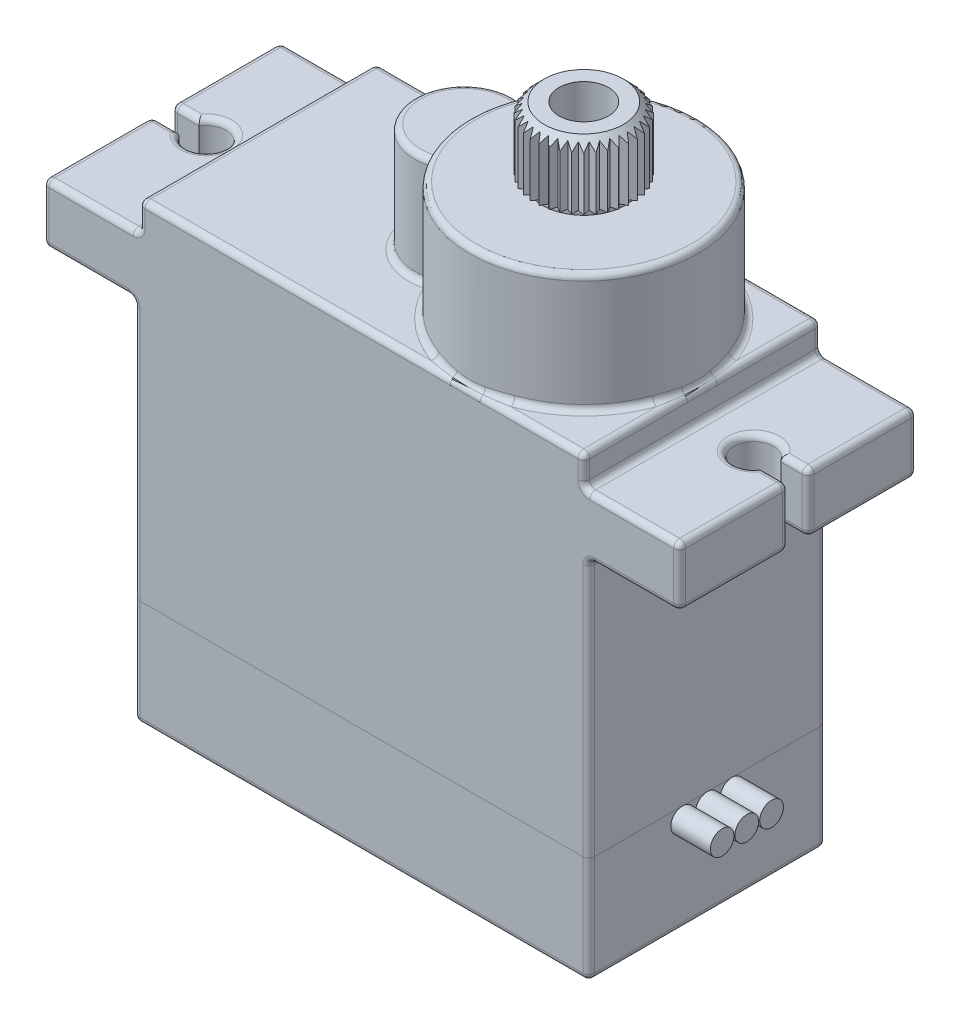
SolidWorks part; units mm, degrees
ref_plane "Front Plane" through (0, 0, 0) normal (0, 0, 1) x (1, 0, 0)
ref_plane "Top Plane" through (0, 0, 0) normal (0, 1, 0) x (1, 0, 0)
ref_plane "Right Plane" through (0, 0, 0) normal (1, 0, 0) x (0, 0, -1)
sketch "Sketch1" plane through (0, 0, 0) normal (0, 1, 0) x (1, 0, 0)
  line L1 (-11.5, -6) -> (11.5, -6)
  line L2 (-11.5, -6) -> (-11.5, 6)
  line L3 (-11.5, 6) -> (11.5, 6)
  line L4 (11.5, -6) -> (11.5, 6)
  line L5 (-11.5, -6) -> (11.5, 6) construction
  line L6 (-11.5, 6) -> (11.5, -6) construction
  point P0 (0, 0)
  dimension "D1" = 12
  dimension "D2" = 23
extrude "Boss-Extrude1" add sketch "Sketch1" along normal blind 18.5
sketch "Sketch2" plane through (0, 18.5, 0) normal (0, 1, 0) x (1, 0, 0)
  line L0 (11.5, 6) -> (-11.5, 6) construction
  line L1 (-16.1, -6) -> (16.1, -6)
  line L2 (-16.1, -6) -> (-16.1, 6)
  line L3 (-16.1, 6) -> (16.1, 6)
  line L4 (16.1, -6) -> (16.1, 6)
  line L5 (-16.1, -6) -> (16.1, 6) construction
  line L6 (-16.1, 6) -> (16.1, -6) construction
  point P0 (0, 0)
  dimension "D1" = 32.2
extrude "Boss-Extrude2" add sketch "Sketch2" along normal blind 3
sketch "Sketch3" plane through (0, 21.5, 0) normal (0, 1, 0) x (1, 0, 0)
  line L0 (16.1, 6) -> (-16.1, 6) construction
  line L1 (-11.25, -6) -> (11.25, -6)
  line L2 (-11.25, -6) -> (-11.25, 6)
  line L3 (-11.25, 6) -> (11.25, 6)
  line L4 (11.25, -6) -> (11.25, 6)
  line L5 (-11.25, -6) -> (11.25, 6) construction
  line L6 (-11.25, 6) -> (11.25, -6) construction
  point P0 (0, 0)
  dimension "D1" = 22.5
extrude "Boss-Extrude3" add sketch "Sketch3" along normal blind 1.5
sketch "Sketch4" plane through (0, 23, 0) normal (0, 1, 0) x (1, 0, 0)
  line L0 (-11.25, 6) -> (-11.25, -6) construction
  line L1 (5.25, 5.75) -> (5.25, 6) construction
  line L2 (11.25, 6) -> (-11.25, 6) construction
  line L3 (11, 0) -> (11.25, 0) construction
  line L4 (11.25, -6) -> (11.25, 6) construction
  line L5 (5.25, -5.75) -> (5.25, -6) construction
  line L6 (-11.25, -6) -> (11.25, -6) construction
  circle A0 centre (5.25, 0) radius 5.75
  point P5 (-11.25, 0)
  dimension "D1" = 11.5
extrude "Boss-Extrude4" add sketch "Sketch4" along normal blind 6
sketch "Sketch5" plane through (0, 23, 0) normal (0, 1, 0) x (1, 0, 0)
  line L0 (-11.25, 6) -> (-11.25, -6) construction
  circle A0 centre (-0.8, 0) radius 2.5
  circle A1 centre (5.25, 0) radius 5.75 construction
  circle A2 centre (5.25, 0) radius 5.75 construction
  point P2 (-3.3, 0)
  point P5 (-11.25, 0)
  point P6 (11, 0)
  dimension "D1" = 5
  dimension "D2" = 14.3
extrude "Boss-Extrude5" add sketch "Sketch5" along normal blind 5.5
sketch "Sketch6" plane through (0, 21.5, 0) normal (0, 1, 0) x (1, 0, 0)
  line L0 (-11.25, 6) -> (-11.25, -6) construction
  line L1 (0, 6) -> (0, -6) construction
  line L2 (11.25, 6) -> (-11.25, 6) construction
  line L3 (-11.25, -6) -> (11.25, -6) construction
  line L4 (-14.716, 0.5) -> (-16.1, 0.5)
  line L5 (-16.1, 6) -> (-16.1, -6) construction
  line L6 (-14.716, -0.5) -> (-16.1, -0.5)
  line L7 (-16.1, 0.5) -> (-16.1, -0.5)
  line L8 (16.1, 0.5) -> (16.1, -0.5)
  line L9 (14.716, -0.5) -> (16.1, -0.5)
  line L10 (14.716, 0.5) -> (16.1, 0.5)
  arc A0 (-14.716, -0.5) -> (-14.716, 0.5) centre (-13.85, 0) ccw
  arc A1 (14.716, -0.5) -> (14.716, 0.5) centre (13.85, 0) cw
  point P4 (-11.25, 0)
  dimension "D1" = 2
  dimension "D2" = 27.7
  dimension "D3" = 1
extrude "Cut-Extrude1" cut sketch "Sketch6" against normal through all
sketch "Sketch7" plane through (0, 29, 0) normal (0, 1, 0) x (1, 0, 0)
  circle A0 centre (5.25, 0) radius 2.5
  dimension "D1" = 5
extrude "Boss-Extrude6" add sketch "Sketch7" along normal blind 3.5
sketch "Sketch8" plane through (11.5, 0, 0) normal (1, 0, 0) x (0, 0, -1)
  line L0 (-1.25, 4.8) -> (1.25, 4.8) construction
  line L1 (-6, 0) -> (6, 0) construction
  circle A0 centre (-1.25, 4.8) radius 0.6
  circle A1 centre (0, 4.8) radius 0.6
  circle A2 centre (1.25, 4.8) radius 0.6
  dimension "D1" = 1.2
  dimension "D2" = 4.8
  dimension "D3" = 2.5
extrude "Boss-Extrude8" add sketch "Sketch8" along normal blind 2
fillet "Fillet1" radius 0.3 56 edges at (11.5, 0, 0) (11.5, 18.5, 0) (15.408, 18.5, 0.5) (12.85, 18.5, 0) (15.408, 18.5, -0.5) (15.408, 21.5, 0.5) (15.408, 21.5, -0.5) (12.85, 21.5, 0) (-11.25, 23, 0) (-15.408, 21.5, -0.5) (-11.25, 21.5, 0) (-15.408, 21.5, 0.5) (-12.85, 21.5, 0) (-16.1, 20, 0.5) (-16.1, 21.5, 3.25) (-16.1, 21.5, -3.25) (-16.1, 20, -0.5) (-16.1, 18.5, 3.25) (-16.1, 18.5, -3.25) (-15.408, 18.5, -0.5) (-12.85, 18.5, 0) (-15.408, 18.5, 0.5) (-11.5, 18.5, 0) (-11.5, 0, 0) (11.25, 23, 0) (11.25, 21.5, 0) (16.1, 21.5, 3.25) (16.1, 20, 0.5) (16.1, 18.5, 3.25) (16.1, 18.5, -3.25) (16.1, 20, -0.5) (16.1, 21.5, -3.25) (11.5, 9.25, -6) (13.8, 18.5, -6) (16.1, 20, -6) (13.675, 21.5, -6) (11.25, 22.25, -6) (0, 23, -6) (-11.25, 22.25, -6) (-13.675, 21.5, -6) (-16.1, 20, -6) (-13.8, 18.5, -6) (-11.5, 9.25, -6) (0, 0, -6) (-11.5, 9.25, 6) (-13.8, 18.5, 6) (-16.1, 20, 6) (-13.675, 21.5, 6) (-11.25, 22.25, 6) (0, 23, 6) (11.25, 22.25, 6) (13.675, 21.5, 6) (16.1, 20, 6) (13.8, 18.5, 6) (11.5, 9.25, 6) (0, 0, 6)
fillet "Fillet2" radius 0.3 10 edges at (5.25, 23, 5.75) (9.3159, 23, 4.0659) (11, 23, 0) (9.3159, 23, -4.0659) (5.25, 23, -5.75) (-3.3, 23, 0) (1.8189, 23, 4.6141) (1.8189, 23, -4.6141) (5.25, 29, 5.75) (-3.3, 28.5, 0)
chamfer "Chamfer1" distance 0.5 angle 45 1 edges at (5.25, 32.5, 2.5)
sketch "Sketch10" plane through (0, 32.5, 0) normal (0, 1, 0) x (1, 0, 0)
  line L0 (5.25, 0) -> (5.0321, 2.4905) construction
  line L1 (5.25, 0) -> (5.4679, 2.4905) construction
  line L2 (5.25, 0) -> (5.25, 2.5) construction
  line L3 (5.0321, 2.4905) -> (5.25, 2.2)
  line L4 (5.25, 2.2) -> (5.4679, 2.4905)
  line L5 (5.632, 2.1666) -> (5.897, 2.4148)
  line L6 (5.4679, 2.4905) -> (5.632, 2.1666)
  line L7 (6.0024, 2.0673) -> (6.3065, 2.2658)
  line L8 (5.897, 2.4148) -> (6.0024, 2.0673)
  line L9 (6.35, 1.9053) -> (6.6839, 2.0479)
  line L10 (6.3065, 2.2658) -> (6.35, 1.9053)
  line L11 (6.6641, 1.6853) -> (7.0178, 1.7678)
  line L12 (6.6839, 2.0479) -> (6.6641, 1.6853)
  line L13 (6.9353, 1.4141) -> (7.2979, 1.4339)
  line L14 (7.0178, 1.7678) -> (6.9353, 1.4141)
  line L15 (7.1553, 1.1) -> (7.5158, 1.0565)
  line L16 (7.2979, 1.4339) -> (7.1553, 1.1)
  line L17 (7.3173, 0.7524) -> (7.6648, 0.647)
  line L18 (7.5158, 1.0565) -> (7.3173, 0.7524)
  line L19 (7.4166, 0.382) -> (7.7405, 0.2179)
  line L20 (7.6648, 0.647) -> (7.4166, 0.382)
  line L21 (7.45, 0) -> (7.7405, -0.2179)
  line L22 (7.7405, 0.2179) -> (7.45, 0)
  line L23 (7.4166, -0.382) -> (7.6648, -0.647)
  line L24 (7.7405, -0.2179) -> (7.4166, -0.382)
  line L25 (7.3173, -0.7524) -> (7.5158, -1.0565)
  line L26 (7.6648, -0.647) -> (7.3173, -0.7524)
  line L27 (7.1553, -1.1) -> (7.2979, -1.4339)
  line L28 (7.5158, -1.0565) -> (7.1553, -1.1)
  line L29 (6.9353, -1.4141) -> (7.0178, -1.7678)
  line L30 (7.2979, -1.4339) -> (6.9353, -1.4141)
  line L31 (6.6641, -1.6853) -> (6.6839, -2.0479)
  line L32 (7.0178, -1.7678) -> (6.6641, -1.6853)
  line L33 (6.35, -1.9053) -> (6.3065, -2.2658)
  line L34 (6.6839, -2.0479) -> (6.35, -1.9053)
  line L35 (6.0024, -2.0673) -> (5.897, -2.4148)
  line L36 (6.3065, -2.2658) -> (6.0024, -2.0673)
  line L37 (5.632, -2.1666) -> (5.4679, -2.4905)
  line L38 (5.897, -2.4148) -> (5.632, -2.1666)
  line L39 (5.25, -2.2) -> (5.0321, -2.4905)
  line L40 (5.4679, -2.4905) -> (5.25, -2.2)
  line L41 (4.868, -2.1666) -> (4.603, -2.4148)
  line L42 (5.0321, -2.4905) -> (4.868, -2.1666)
  line L43 (4.4976, -2.0673) -> (4.1935, -2.2658)
  line L44 (4.603, -2.4148) -> (4.4976, -2.0673)
  line L45 (4.15, -1.9053) -> (3.8161, -2.0479)
  line L46 (4.1935, -2.2658) -> (4.15, -1.9053)
  line L47 (3.8359, -1.6853) -> (3.4822, -1.7678)
  line L48 (3.8161, -2.0479) -> (3.8359, -1.6853)
  line L49 (3.5647, -1.4141) -> (3.2021, -1.4339)
  line L50 (3.4822, -1.7678) -> (3.5647, -1.4141)
  line L51 (3.3447, -1.1) -> (2.9842, -1.0565)
  line L52 (3.2021, -1.4339) -> (3.3447, -1.1)
  line L53 (3.1827, -0.7524) -> (2.8352, -0.647)
  line L54 (2.9842, -1.0565) -> (3.1827, -0.7524)
  line L55 (3.0834, -0.382) -> (2.7595, -0.2179)
  line L56 (2.8352, -0.647) -> (3.0834, -0.382)
  line L57 (3.05, 0) -> (2.7595, 0.2179)
  line L58 (2.7595, -0.2179) -> (3.05, 0)
  line L59 (3.0834, 0.382) -> (2.8352, 0.647)
  line L60 (2.7595, 0.2179) -> (3.0834, 0.382)
  line L61 (3.1827, 0.7524) -> (2.9842, 1.0565)
  line L62 (2.8352, 0.647) -> (3.1827, 0.7524)
  line L63 (3.3447, 1.1) -> (3.2021, 1.4339)
  line L64 (2.9842, 1.0565) -> (3.3447, 1.1)
  line L65 (3.5647, 1.4141) -> (3.4822, 1.7678)
  line L66 (3.2021, 1.4339) -> (3.5647, 1.4141)
  line L67 (3.8359, 1.6853) -> (3.8161, 2.0479)
  line L68 (3.4822, 1.7678) -> (3.8359, 1.6853)
  line L69 (4.15, 1.9053) -> (4.1935, 2.2658)
  line L70 (3.8161, 2.0479) -> (4.15, 1.9053)
  line L71 (4.4976, 2.0673) -> (4.603, 2.4148)
  line L72 (4.1935, 2.2658) -> (4.4976, 2.0673)
  line L73 (4.868, 2.1666) -> (5.0321, 2.4905)
  line L74 (4.603, 2.4148) -> (4.868, 2.1666)
  circle A0 centre (5.25, 0) radius 2.5 construction
  arc A1 (5.4679, 2.4905) -> (5.0321, 2.4905) centre (5.25, 0) ccw
  circle A2 centre (5.25, 0) radius 2.2 construction
  arc A3 (5.897, 2.4148) -> (5.4679, 2.4905) centre (5.25, 0) ccw
  arc A4 (6.3065, 2.2658) -> (5.897, 2.4148) centre (5.25, 0) ccw
  arc A5 (6.6839, 2.0479) -> (6.3065, 2.2658) centre (5.25, 0) ccw
  arc A6 (7.0178, 1.7678) -> (6.6839, 2.0479) centre (5.25, 0) ccw
  arc A7 (7.2979, 1.4339) -> (7.0178, 1.7678) centre (5.25, 0) ccw
  arc A8 (7.5158, 1.0565) -> (7.2979, 1.4339) centre (5.25, 0) ccw
  arc A9 (7.6648, 0.647) -> (7.5158, 1.0565) centre (5.25, 0) ccw
  arc A10 (7.7405, 0.2179) -> (7.6648, 0.647) centre (5.25, 0) ccw
  arc A11 (7.7405, -0.2179) -> (7.7405, 0.2179) centre (5.25, 0) ccw
  arc A12 (7.6648, -0.647) -> (7.7405, -0.2179) centre (5.25, 0) ccw
  arc A13 (7.5158, -1.0565) -> (7.6648, -0.647) centre (5.25, 0) ccw
  arc A14 (7.2979, -1.4339) -> (7.5158, -1.0565) centre (5.25, 0) ccw
  arc A15 (7.0178, -1.7678) -> (7.2979, -1.4339) centre (5.25, 0) ccw
  arc A16 (6.6839, -2.0479) -> (7.0178, -1.7678) centre (5.25, 0) ccw
  arc A17 (6.3065, -2.2658) -> (6.6839, -2.0479) centre (5.25, 0) ccw
  arc A18 (5.897, -2.4148) -> (6.3065, -2.2658) centre (5.25, 0) ccw
  arc A19 (5.4679, -2.4905) -> (5.897, -2.4148) centre (5.25, 0) ccw
  arc A20 (5.0321, -2.4905) -> (5.4679, -2.4905) centre (5.25, 0) ccw
  arc A21 (4.603, -2.4148) -> (5.0321, -2.4905) centre (5.25, 0) ccw
  arc A22 (4.1935, -2.2658) -> (4.603, -2.4148) centre (5.25, 0) ccw
  arc A23 (3.8161, -2.0479) -> (4.1935, -2.2658) centre (5.25, 0) ccw
  arc A24 (3.4822, -1.7678) -> (3.8161, -2.0479) centre (5.25, 0) ccw
  arc A25 (3.2021, -1.4339) -> (3.4822, -1.7678) centre (5.25, 0) ccw
  arc A26 (2.9842, -1.0565) -> (3.2021, -1.4339) centre (5.25, 0) ccw
  arc A27 (2.8352, -0.647) -> (2.9842, -1.0565) centre (5.25, 0) ccw
  arc A28 (2.7595, -0.2179) -> (2.8352, -0.647) centre (5.25, 0) ccw
  arc A29 (2.7595, 0.2179) -> (2.7595, -0.2179) centre (5.25, 0) ccw
  arc A30 (2.8352, 0.647) -> (2.7595, 0.2179) centre (5.25, 0) ccw
  arc A31 (2.9842, 1.0565) -> (2.8352, 0.647) centre (5.25, 0) ccw
  arc A32 (3.2021, 1.4339) -> (2.9842, 1.0565) centre (5.25, 0) ccw
  arc A33 (3.4822, 1.7678) -> (3.2021, 1.4339) centre (5.25, 0) ccw
  arc A34 (3.8161, 2.0479) -> (3.4822, 1.7678) centre (5.25, 0) ccw
  arc A35 (4.1935, 2.2658) -> (3.8161, 2.0479) centre (5.25, 0) ccw
  arc A36 (4.603, 2.4148) -> (4.1935, 2.2658) centre (5.25, 0) ccw
  arc A37 (5.0321, 2.4905) -> (4.603, 2.4148) centre (5.25, 0) ccw
  point P114 (5.25, 0)
  dimension "D1" = 4.4
  dimension "D2" = 10
  dimension "D3" = 36
extrude "Cut-Extrude2" cut sketch "Sketch10" against normal up to surface (3.5 mm away) contours L69 A35 L70 | L67 A34 L68 | L65 A33 L66 | L63 A32 L64 | L61 A31 L62 | L59 A30 L60 | L57 A29 L58 | L55 A28 L56 | L53 A27 L54 | L51 A26 L52 | L49 A25 L50 | L45 A23 L46 | L43 A22 L44 | L41 A21 L42 | L39 A20 L40 | L37 A19 L38 | L35 A18 L36 | L33 A17 L34 | L31 A16 L32 | L29 A15 L30 | L27 A14 L28 | L25 A13 L26 | L23 A12 L24 | L21 A11 L22 | L19 A10 L20 | L17 A9 L18 | L15 A8 L16 | L13 A7 L14 | L11 A6 L12 | L9 A5 L10 | L7 A4 L8 | L5 A3 L6 | L4 A1 L3 | L73 A37 L74 | L71 A36 L72 | L47 A24 L48 region at (5.25, 32.5, -2.3979) region at (4.8336, 32.5, -2.3614) region at (5.6664, 32.5, -2.3614) region at (4.4299, 32.5, -2.2533) region at (6.0701, 32.5, -2.2533) region at (4.0511, 32.5, -2.0766) region at (6.4489, 32.5, -2.0766) region at (3.7087, 32.5, -1.8369) region at (6.7913, 32.5, -1.8369) region at (3.4131, 32.5, -1.5413) region at (7.0869, 32.5, -1.5413) region at (3.1734, 32.5, -1.1989) region at (7.3266, 32.5, -1.1989) region at (2.9967, 32.5, -0.8201) region at (7.5033, 32.5, -0.8201) region at (2.8886, 32.5, -0.4164) region at (7.6114, 32.5, -0.4164) region at (2.8521, 32.5, 0) region at (7.6479, 32.5, 0) region at (2.8886, 32.5, 0.4164) region at (7.6114, 32.5, 0.4164) region at (2.9967, 32.5, 0.8201) region at (7.5033, 32.5, 0.8201) region at (3.1734, 32.5, 1.1989) region at (7.3266, 32.5, 1.1989) region at (3.4131, 32.5, 1.5413) region at (7.0869, 32.5, 1.5413) region at (6.7913, 32.5, 1.8369) region at (4.0511, 32.5, 2.0766) region at (6.4489, 32.5, 2.0766) region at (4.4299, 32.5, 2.2533) region at (6.0701, 32.5, 2.2533) region at (4.8336, 32.5, 2.3614) region at (5.6664, 32.5, 2.3614) region at (5.25, 32.5, 2.3979) up to face at (5.25, 29, 5.45)
sketch "Sketch11" plane through (0, 0, 0) normal (0, 0, 1) x (1, 0, 0)
  line L0 (5.25, 32.5) -> (5.25, 27.5426) construction
  line L1 (7.9405, 29) -> (7.3405, 29)
  line L2 (7.9405, 29) -> (7.9405, 29.3)
  line L3 (7.9405, 29.3) -> (7.3405, 29.3)
  line L4 (7.3405, 29) -> (7.3405, 29.3)
  line L5 (7.25, 32.5) -> (3.25, 32.5) construction
  line L7 (10.7, 29) -> (-0.2, 29) construction
  line L8 (7.7405, 29) -> (7.7405, 32) construction
  dimension "D1" = 0.3
  dimension "D2" = 0.4
  dimension "D3" = 0.2
revolve "Cut-Revolve1" cut sketch "Sketch11" angle 360 about L0
ref_plane "Plane1" through (0, 5.4, 0) normal (0, 1, 0) x (1, 0, 0)
split line "Split Line1"
sketch "Sketch14" plane through (0, 32.5, 0) normal (0, 1, 0) x (1, 0, 0)
  circle A0 centre (5.25, 0) radius 1.25
  dimension "D1" = 2.5
extrude "Cut-Extrude3" cut sketch "Sketch14" against normal blind 2.5
